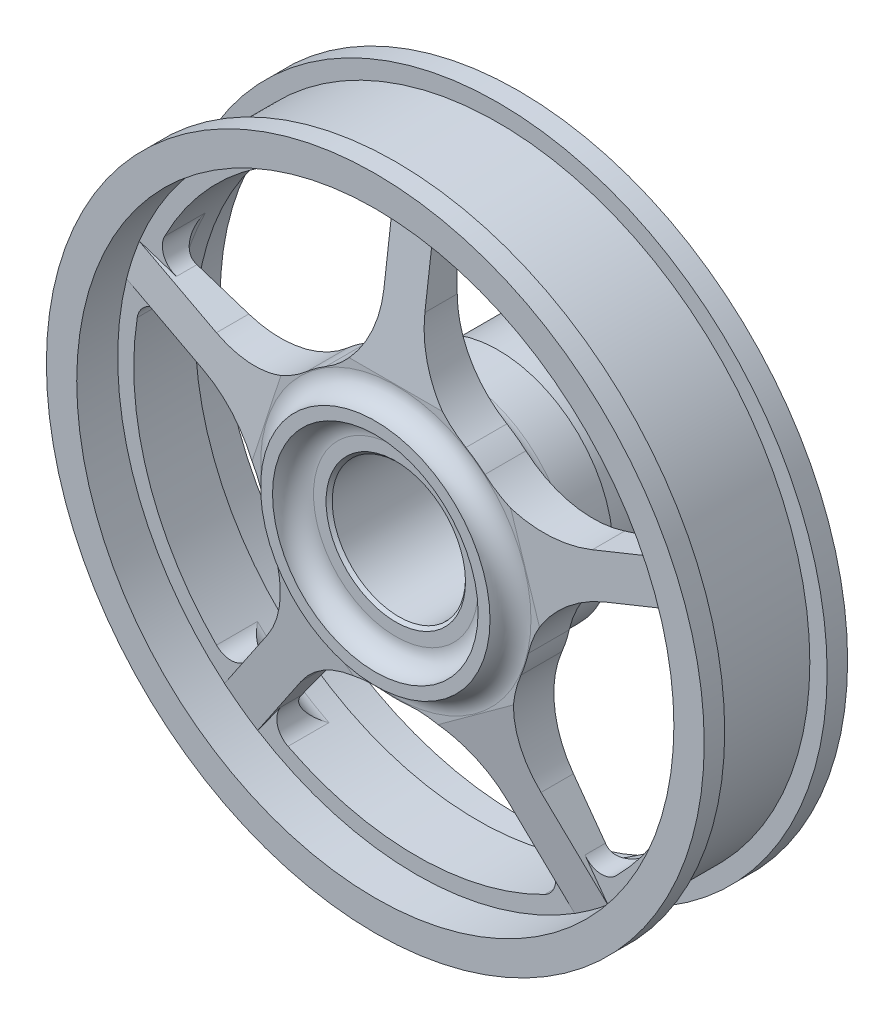
SolidWorks part; units mm, degrees
ref_plane "Front Plane" through (0, 0, 0) normal (0, 0, 1) x (1, 0, 0)
ref_plane "Top Plane" through (0, 0, 0) normal (0, 1, 0) x (1, 0, 0)
ref_plane "Right Plane" through (0, 0, 0) normal (1, 0, 0) x (0, 0, -1)
sketch "Sketch2" plane through (0, 0, 0) normal (0, 0, 1) x (1, 0, 0)
  line L0 (0, 73.8131) -> (0, -75.6428) construction
  line L1 (-85.7336, 0) -> (85.2945, 0) construction
  circle A0 centre (0, 0) radius 3.2532
  circle A1 centre (0, 0) radius 5.0174
extrude "Boss-Extrude1" add sketch "Sketch2" along normal mid plane 10
sketch "Sketch3" plane through (0, 0, 0) normal (0, 0, 1) x (1, 0, 0)
  circle A0 centre (0, 0) radius 5.0174
  circle A1 centre (0, 0) radius 5.6
extrude "Boss-Extrude2" add sketch "Sketch3" along normal blind 6
sketch "Sketch4" plane through (0, 0, 0) normal (0, 0, 1) x (1, 0, 0)
  line L0 (0, 15.2414) -> (0, -10.6306) construction
  line L1 (-14.6864, 0) -> (17.6749, 0) construction
ref_plane "Plane1" through (0, 0, 4) normal (0, 0, 1) x (1, 0, 0)
sketch "Sketch8" plane through (0, 0, 4) normal (0, 0, 1) x (1, 0, 0)
  circle A0 centre (0, 0) radius 5.0174
  circle A1 centre (0, 0) radius 6.6377
extrude "Boss-Extrude6" add sketch "Sketch8" along normal mid plane 2
sketch "Sketch9" plane through (0, 0, 0) normal (1, 0, 0) x (0, 0, -1)
  line L1 (-5, 6.6377) -> (-4, 14.5749)
  line L2 (-4, 14.2296) -> (-4, -14.2296) construction
  line L3 (-4, 14.5749) -> (-3, 14.5749)
  line L4 (-3, 14.5749) -> (-3, 6.6377)
  line L5 (-5, 6.6377) -> (-5, 5.987)
  line L6 (-5, 6.6377) -> (-5, -6.6377) construction
  line L7 (-5, 5.987) -> (-3, 5.987)
  line L8 (-3, -6.6377) -> (-3, 6.6377) construction
  line L9 (-3, 5.987) -> (-3, 6.6377)
  dimension "D1" = 7.9373
extrude "Boss-Extrude9" add sketch "Sketch9" along normal mid plane 2 contours L4 L9 L7 L5 L1 L3
pattern_circular "CirPattern1" count 5 over 360 about axis through (0, 0, 5) along (0, 0, -1) of "Boss-Extrude9"
fillet "Fillet2" radius 5 1 edges at (1, 6.5619, 4)
fillet "Fillet3" radius 5 9 edges at (5.9317, 2.9788, 4) (4.666, -4.7209, 4) (6.5498, 1.0767, 4) (-3.048, -5.8965, 4) (3.048, -5.8965, 4) (-6.5498, 1.0767, 4) (-4.666, -4.7209, 4) (-5.9317, 2.9788, 4) (-1, 6.5619, 4)
sketch "Sketch12" plane through (0, 0, 4) normal (0, 0, 1) x (1, 0, 0)
  circle A0 centre (0, 0) radius 14.5749
  circle A1 centre (0, 0) radius 13.7908
extrude "Boss-Extrude10" add sketch "Sketch12" against normal blind 3
sketch "Sketch13" plane through (0, 0, 6) normal (0, 0, 1) x (1, 0, 0)
  circle A0 centre (0, 0) radius 14.5749
  circle A1 centre (0, 0) radius 16.0566
extrude "Boss-Extrude11" add sketch "Sketch13" against normal blind 1 separate body
sketch "Sketch14" plane through (0, 0, 5) normal (0, 0, -1) x (-1, 0, 0)
  circle A0 centre (0, 0) radius 14.5749
  circle A1 centre (0, 0) radius 15.2115
extrude "Boss-Extrude12" add sketch "Sketch14" along normal blind 5
sketch "Sketch15" plane through (0, 0, 0) normal (0, 0, -1) x (-1, 0, 0)
  circle A0 centre (0, 0) radius 14.5749
  circle A1 centre (0, 0) radius 16.0566
extrude "Boss-Extrude13" add sketch "Sketch15" along normal blind 1
fillet "Fillet5" radius 1 1 edges at (-1, 13.7545, 3.5)
fillet "Fillet6" radius 1 9 edges at (13.3904, 3.2993, 3.5) (12.7723, 5.2014, 3.5) (7.2757, -11.7154, 3.5) (8.8937, -10.5399, 3.5) (-8.8937, -10.5399, 3.5) (-7.2757, -11.7154, 3.5) (-12.7723, 5.2014, 3.5) (-13.3904, 3.2993, 3.5) (1, 13.7545, 3.5)
fillet "Fillet7" radius 1 1 edges at (0, 13.7908, 3)
fillet "Fillet8" radius 1 4 edges at (13.1159, 4.2616, 3) (8.1061, -11.157, 3) (-8.1061, -11.157, 3) (-13.1159, 4.2616, 3)
fillet "Fillet9" radius 1 1 edges at (5.6, 0, 3)
fillet "Fillet10" radius 1 1 edges at (5.0174, 0, 5)
fillet "Fillet11" radius 1 1 edges at (5.6, 0, 5)
chamfer "Chamfer8" distance 0.15 angle 45 1 edges at (3.2532, 0, -5)
chamfer "Chamfer9" distance 0.15 angle 45 2 edges at (3.2532, 0, 5) (5.0174, 0, -5)
